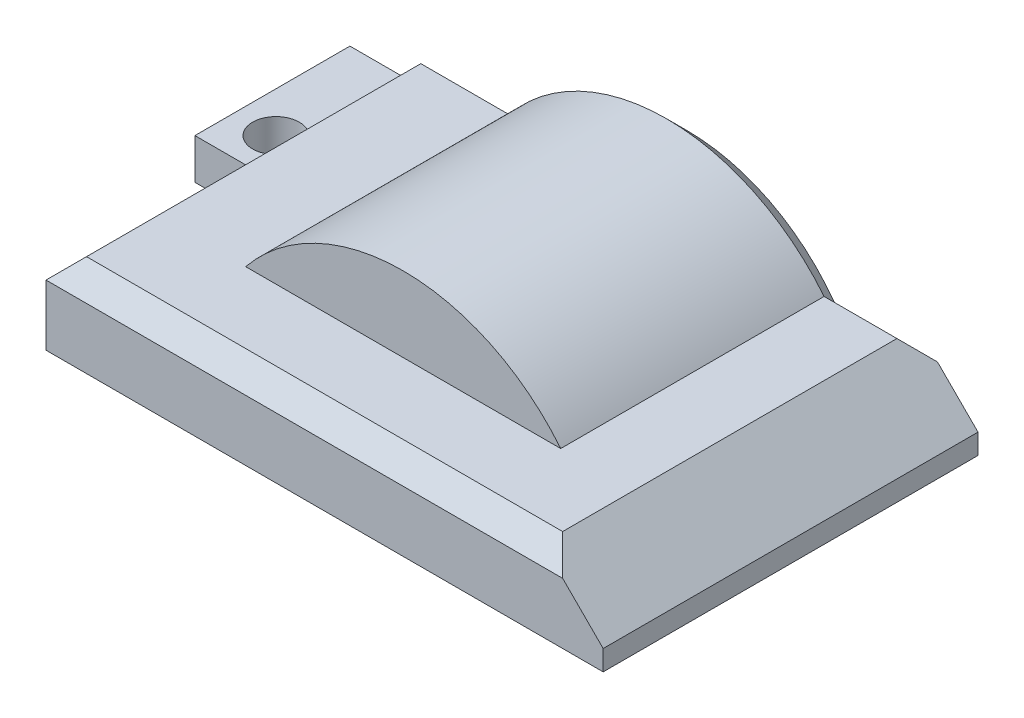
SolidWorks part; units mm, degrees
ref_plane "前视基准面" through (0, 0, 0) normal (0, 0, 1) x (1, 0, 0)
ref_plane "上视基准面" through (0, 0, 0) normal (0, 1, 0) x (1, 0, 0)
ref_plane "右视基准面" through (0, 0, 0) normal (1, 0, 0) x (0, 0, -1)
other "Configuration Table"
sketch "草图1" plane through (0, 0, 0) normal (0, 1, 0) x (1, 0, 0)
  line L0 (-2, -2) -> (-2, 18)
  line L1 (0, 0) -> (23.5, 0)
  line L2 (0, 0) -> (0, 16)
  line L3 (0, 16) -> (23.5, 16)
  line L4 (23.5, 0) -> (23.5, 16)
  line L5 (-2, 18) -> (25.5, 18)
  line L6 (25.5, -2) -> (25.5, 18)
  line L7 (-2, -2) -> (25.5, -2)
  dimension "D1" = 23.5
  dimension "D2" = 16
  dimension "D3" = 2
extrude "凸台-拉伸1" add sketch "草图1" along normal blind 2
sketch "草图2" plane through (23.5, 0, 0) normal (-1, 0, 0) x (0, 0, 1)
  line L0 (-16, 1.5) -> (0, 1.5) construction
  line L1 (-16, 2) -> (-16, 0) construction
  line L2 (0, 2) -> (0, 0) construction
  line L3 (0, 0) -> (-16, 0) construction
  line L5 (-16, 1.5) -> (-14.6, 1.5)
  line L6 (-16, 1.5) -> (-16, 0)
  line L7 (-16, 0) -> (-14.6, 0)
  line L8 (-14.6, 1.5) -> (-14.6, 0)
  line L9 (0, 1.5) -> (-1.4, 1.5)
  line L10 (0, 1.5) -> (0, 0)
  line L11 (0, 0) -> (-1.4, 0)
  line L12 (-1.4, 1.5) -> (-1.4, 0)
  dimension "D1" = 1.5
  dimension "D2" = 1.4
  dimension "D3" = 1.4
extrude "切除-拉伸1" cut sketch "草图2" against normal up to next
sketch "草图3" plane through (0, 0, 0) normal (1, 0, 0) x (0, 0, -1)
  line L0 (14.6, 1.5) -> (14.6, 0) construction
  line L1 (16, 0) -> (16, 1.5) construction
  line L2 (16, 1.5) -> (14.6, 1.5) construction
  line L3 (14.6, 1.5) -> (14.6, 0)
  line L4 (16, 0) -> (16, 1.5)
  line L5 (16, 1.5) -> (14.6, 1.5)
  line L6 (14.6, 0) -> (16, 0)
extrude "切除-拉伸2" cut sketch "草图3" against normal up to next
sketch "草图4" plane through (0, 0, -18) normal (0, 0, -1) x (-1, 0, 0)
  line L0 (-25.5, 2) -> (-25.5, 0) construction
  line L1 (-25.5, 0) -> (2, 0) construction
  line L2 (-20.163, 2) -> (-2.097, 2)
  line L3 (-25.5, 2) -> (2, 2) construction
  arc A0 (-2.097, 2) -> (-20.163, 2) centre (-11.13, -2.29) ccw
  dimension "D1" = 14.37
  dimension "D3" = 20
  dimension "D2" = 2.29
extrude "凸台-拉伸2" add sketch "草图4" against normal up to surface (2 mm away) up to face at (11.75, 1.25, -16)
sketch "草图5" plane through (0, 0, -16) normal (0, 0, 1) x (1, 0, 0)
  line L3 (2.097, 2) -> (3.6764, 2)
  line L5 (18.5836, 2) -> (20.163, 2)
  arc A0 (18.5836, 2) -> (3.6764, 2) centre (11.13, -2.29) ccw
  arc A1 (20.163, 2) -> (2.097, 2) centre (11.13, -2.29) ccw construction
  arc A2 (20.163, 2) -> (2.097, 2) centre (11.13, -2.29) ccw
  dimension "D1" = 1.4
extrude "凸台-拉伸3" add sketch "草图5" along normal blind 11
sketch "草图6" plane through (0, 2, 0) normal (0, 1, 0) x (1, 0, 0)
  line L0 (25.5, -2) -> (25.5, 18) construction
  line L1 (-2, -2) -> (25.5, -2)
  line L2 (-2, -2) -> (-2, 5)
  line L3 (-2, 5) -> (25.5, 5)
  line L4 (25.5, -2) -> (25.5, 5)
  line L5 (2.097, 5) -> (20.163, 5) construction
extrude "凸台-拉伸4" add sketch "草图6" along normal blind 2
sketch "草图7" plane through (0, 0, -5) normal (0, 0, -1) x (-1, 0, 0)
  line L0 (2, 4) -> (-3.3559, 4) construction
  line L1 (-2.097, 2) -> (0, 2) construction
  line L2 (0, 2) -> (2, 2) construction
  line L3 (2, 2) -> (2, 4) construction
  line L4 (-23.5, 2) -> (-20.163, 2) construction
  line L5 (-18.9041, 4) -> (-25.5, 4) construction
  line L6 (-25.5, 4) -> (-25.5, 2) construction
  line L7 (-25.5, 2) -> (-23.5, 2) construction
  line L8 (2, 4) -> (-3.3559, 4)
  line L9 (-2.097, 2) -> (0, 2)
  line L10 (0, 2) -> (2, 2)
  line L11 (2, 2) -> (2, 4)
  line L12 (-23.5, 2) -> (-20.163, 2)
  line L13 (-18.9041, 4) -> (-25.5, 4)
  line L14 (-25.5, 4) -> (-25.5, 2)
  line L15 (-25.5, 2) -> (-23.5, 2)
  arc A0 (-2.097, 2) -> (-3.3559, 4) centre (-11.13, -2.29) ccw construction
  arc A1 (-18.9041, 4) -> (-20.163, 2) centre (-11.13, -2.29) ccw construction
  arc A2 (-2.097, 2) -> (-3.3559, 4) centre (-11.13, -2.29) ccw
  arc A3 (-18.9041, 4) -> (-20.163, 2) centre (-11.13, -2.29) ccw
extrude "凸台-拉伸5" add sketch "草图7" along normal up to surface (13 mm away) up to face at (11.5433, 2.285, -18)
sketch "草图8" plane through (0, 0, -5) normal (0, 0, 1) x (1, 0, 0)
  line L0 (3.3559, 4) -> (18.9041, 4)
  arc A0 (18.9041, 4) -> (3.3559, 4) centre (11.13, -2.29) ccw construction
  arc A1 (18.9041, 4) -> (3.3559, 4) centre (11.13, -2.29) ccw
extrude "凸台-拉伸6" add sketch "草图8" along normal blind 1
chamfer "倒角1" distance 3 angle 45 1 edges at (25.5, 4, -8)
sketch "草图9" plane through (0, 0, 0) normal (0, -1, 0) x (1, 0, 0)
  line L0 (-2, -14.6) -> (-2, 2) construction
  line L1 (25.5, -18) -> (-2, -18) construction
  line L3 (-2, -18) -> (-5.5, -18)
  line L4 (-2, -18) -> (-2, -10.35)
  line L5 (-2, -10.35) -> (-5.5, -10.35)
  line L6 (-5.5, -18) -> (-5.5, -10.35)
  circle A0 centre (-3.5, -12.35) radius 1.15
  dimension "D1" = 1.5
  dimension "D2" = 5.65
  dimension "D3" = 2.3
  dimension "D4" = 2
  dimension "D5" = 2
extrude "凸台-拉伸7" add sketch "草图9" against normal blind 2
sketch "草图10" plane through (-2, 0, 0) normal (1, 0, 0) x (0, 0, -1)
  line L4 (16, 0) -> (16, 1.5)
  line L5 (16, 1.5) -> (14.6, 1.5)
  line L6 (14.6, 1.5) -> (14.6, 0)
  line L7 (14.6, 0) -> (16, 0)
  line L8 (16, 0) -> (16, 1.5)
  line L9 (16, 1.5) -> (14.6, 1.5)
  line L10 (14.6, 1.5) -> (14.6, 0)
  line L11 (14.6, 0) -> (16, 0)
  dimension "D1" = 0
extrude "切除-拉伸3" cut sketch "草图10" against normal up to next
sketch "草图11" plane through (0, 2, 0) normal (0, 1, 0) x (1, 0, 0)
  circle A0 centre (-3.5, 12.35) radius 2.25
  dimension "D1" = 4.5
extrude "切除-拉伸4" cut sketch "草图11" along normal up to next
sketch "草图14" plane through (-2, 0, 0) normal (-1, 0, 0) x (0, 0, 1)
  line L0 (-10.35, 0) -> (2, 0) construction
  line L1 (0.5, 0) -> (2, 0)
  line L2 (0.5, 0) -> (0.5, 4)
  line L3 (0.5, 4) -> (2, 4)
  line L4 (2, 0) -> (2, 4)
  dimension "D1" = 0.5
extrude "切除-拉伸5" cut sketch "草图14" against normal up to next
chamfer "倒角2" distance 1 angle 45 5 edges at (-2, 4, -16.0135) (20.702, 4, -18) (11.13, 7.71, -18) (0.678, 4, -18) (10.25, 4, 0.5)
sketch "草图12" plane through (0, 0, -14.6) normal (0, 0, -1) x (-1, 0, 0)
  line L5 (-23.5, 1.5) -> (-25, 1.5)
  line L6 (-25, 1.5) -> (-25.5, 1)
  line L7 (-25.5, 1) -> (-25.5, 0)
  line L8 (-25.5, 0) -> (-23.5, 0)
  line L9 (-23.5, 0) -> (-23.5, 1.5)
  line L10 (-23.5, 1.5) -> (-25, 1.5)
  line L11 (-25, 1.5) -> (-25.5, 1)
  line L12 (-25.5, 1) -> (-25.5, 0)
  line L13 (-25.5, 0) -> (-23.5, 0)
  line L14 (-23.5, 0) -> (-23.5, 1.5)
  dimension "D1" = 0
extrude "凸台-拉伸8" add sketch "草图12" along normal up to next
sketch "草图13" plane through (0, 0, -1.4) normal (0, 0, 1) x (1, 0, 0)
  line L5 (25.5, 0) -> (25.5, 1)
  line L6 (25.5, 1) -> (25, 1.5)
  line L7 (25, 1.5) -> (23.5, 1.5)
  line L8 (23.5, 1.5) -> (23.5, 0)
  line L9 (23.5, 0) -> (25.5, 0)
  line L10 (25.5, 0) -> (25.5, 1)
  line L11 (25.5, 1) -> (25, 1.5)
  line L12 (25, 1.5) -> (23.5, 1.5)
  line L13 (23.5, 1.5) -> (23.5, 0)
  line L14 (23.5, 0) -> (25.5, 0)
  dimension "D1" = 0
extrude "凸台-拉伸9" add sketch "草图13" along normal up to next
